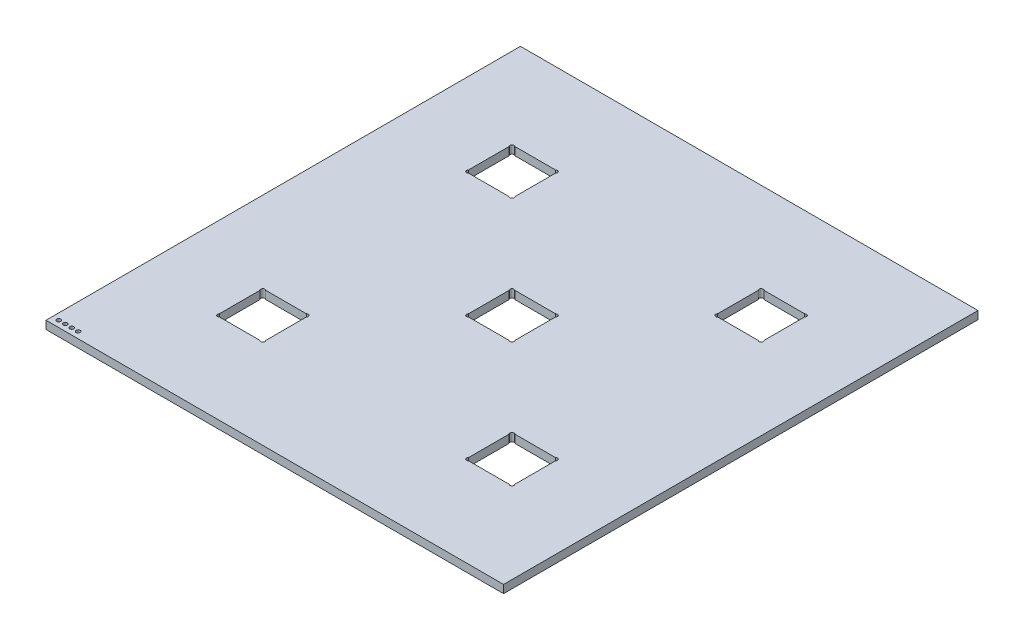
SolidWorks part; units mm, degrees
material "PVC Rigid"
ref_plane "Front" through (0, 0, 0) normal (0, 0, 1) x (1, 0, 0)
ref_plane "Top" through (0, 0, 0) normal (0, 1, 0) x (1, 0, 0)
ref_plane "Right" through (0, 0, 0) normal (1, 0, 0) x (0, 0, -1)
sketch "Sketch1" plane through (0, 0, 0) normal (0, 1, 0) x (1, 0, 0)
  line L1 (-90.3859, -93.726) -> (90.3859, -93.726)
  line L2 (-90.3859, -93.726) -> (-90.3859, 93.726)
  line L3 (-90.3859, 93.726) -> (90.3859, 93.726)
  line L4 (90.3859, -93.726) -> (90.3859, 93.726)
  line L5 (-90.3859, -93.726) -> (90.3859, 93.726) construction
  line L6 (-90.3859, 93.726) -> (90.3859, -93.726) construction
  point P0 (0, 0)
  dimension "D1" = 180.7718
  dimension "D2" = 187.452
extrude "Boss-Extrude1" add sketch "Sketch1" along normal blind 3.175
sketch "Sketch2" plane through (0, 3.175, 0) normal (0, 1, 0) x (1, 0, 0)
  line L0 (-90.3859, 93.726) -> (90.3859, -93.726) construction
  line L2 (-9.144, -9.144) -> (9.144, -9.144)
  line L3 (-9.144, -9.144) -> (-9.144, 9.144)
  line L4 (-9.144, 9.144) -> (9.144, 9.144)
  line L5 (9.144, -9.144) -> (9.144, 9.144)
  line L6 (-9.144, -9.144) -> (9.144, 9.144) construction
  line L7 (-9.144, 9.144) -> (9.144, -9.144) construction
  point P4 (0, 0)
  point P10 (0, 0)
  dimension "D1" = 18.288
  dimension "D2" = 18.288
extrude "Cut-Extrude1" cut sketch "Sketch2" against normal blind 3.175
sketch "Sketch3" plane through (0, 3.175, 0) normal (0, 1, 0) x (1, 0, 0)
  line L0 (9.144, -9.144) -> (8.0215, -9.144) construction
  line L6 (-9.144, -9.144) -> (9.144, -9.144) construction
  line L7 (9.144, -9.144) -> (9.144, -8.0215) construction
  line L8 (9.144, -9.144) -> (9.144, 9.144) construction
  line L9 (9.144, 0) -> (-9.144, 0) construction
  line L10 (-9.144, 9.144) -> (-9.144, -9.144) construction
  line L11 (0, -9.144) -> (0, 9.144) construction
  line L12 (9.144, 9.144) -> (-9.144, 9.144) construction
  circle A4 centre (8.5827, -8.5827) radius 0.7937
  circle A5 centre (-8.5827, -8.5827) radius 0.7937
  circle A6 centre (-8.5827, 8.5827) radius 0.7937
  circle A7 centre (8.5827, 8.5827) radius 0.7937
  dimension "D1" = 1.5875
extrude "Cut-Extrude2" cut sketch "Sketch3" against normal through all
sketch "Sketch8" plane through (0, 3.175, 0) normal (0, 1, 0) x (1, 0, 0)
  line L0 (90.3859, -93.726) -> (-90.3859, 93.726) construction
  line L2 (49.2125, 49.2125) -> (-49.2125, 49.2125) construction
  line L3 (49.2125, 49.2125) -> (49.2125, -49.2125) construction
  line L4 (49.2125, -49.2125) -> (-49.2125, -49.2125) construction
  line L5 (-49.2125, 49.2125) -> (-49.2125, -49.2125) construction
  line L6 (49.2125, 49.2125) -> (-49.2125, -49.2125) construction
  line L7 (49.2125, -49.2125) -> (-49.2125, 49.2125) construction
  point P4 (0, 0)
  point P11 (-49.2125, -49.2125)
  point P12 (-49.2125, 49.2125)
  point P13 (49.2125, 49.2125)
  point P14 (49.2125, -49.2125)
  dimension "D1" = 98.425
pattern_sketch "Sketch-Pattern1" of "Cut-Extrude1", "Cut-Extrude2" driven by "Sketch8"
sketch "Sketch4" plane through (0, 3.175, 0) normal (0, 1, 0) x (1, 0, 0)
  line L0 (-87.8459, -91.186) -> (90.3859, -91.186) construction
  line L1 (-90.3859, -93.726) -> (-87.8459, -93.726) construction
  line L2 (-90.3859, -93.726) -> (-90.3859, -91.186) construction
  line L3 (-90.3859, -91.186) -> (-87.8459, -91.186) construction
  line L4 (-87.8459, -93.726) -> (-87.8459, -91.186) construction
  line L5 (90.3859, -93.726) -> (90.3859, 93.726) construction
  text T0 "TR" font "Consolas" height 3.175
  dimension "D1" = 2.54
extrude "Cut-Extrude3" [suppressed] cut sketch "Sketch4" against normal blind 1.5875
sketch "Sketch9" plane through (0, 3.175, 0) normal (0, 1, 0) x (1, 0, 0)
  line L0 (-90.3859, 93.726) -> (-90.3859, -93.726) construction
  line L1 (-90.3859, -93.726) -> (90.3859, -93.726) construction
  circle A0 centre (-87.8459, -91.186) radius 0.7937
  dimension "D1" = 1.5875
  dimension "D2" = 2.54
  dimension "D3" = 2.54
extrude "Cut-Extrude4" cut sketch "Sketch9" against normal blind 1.27
pattern_linear "LPattern1" count 4 spacing 2.54 along (1, 0, 0) of "Cut-Extrude4"
